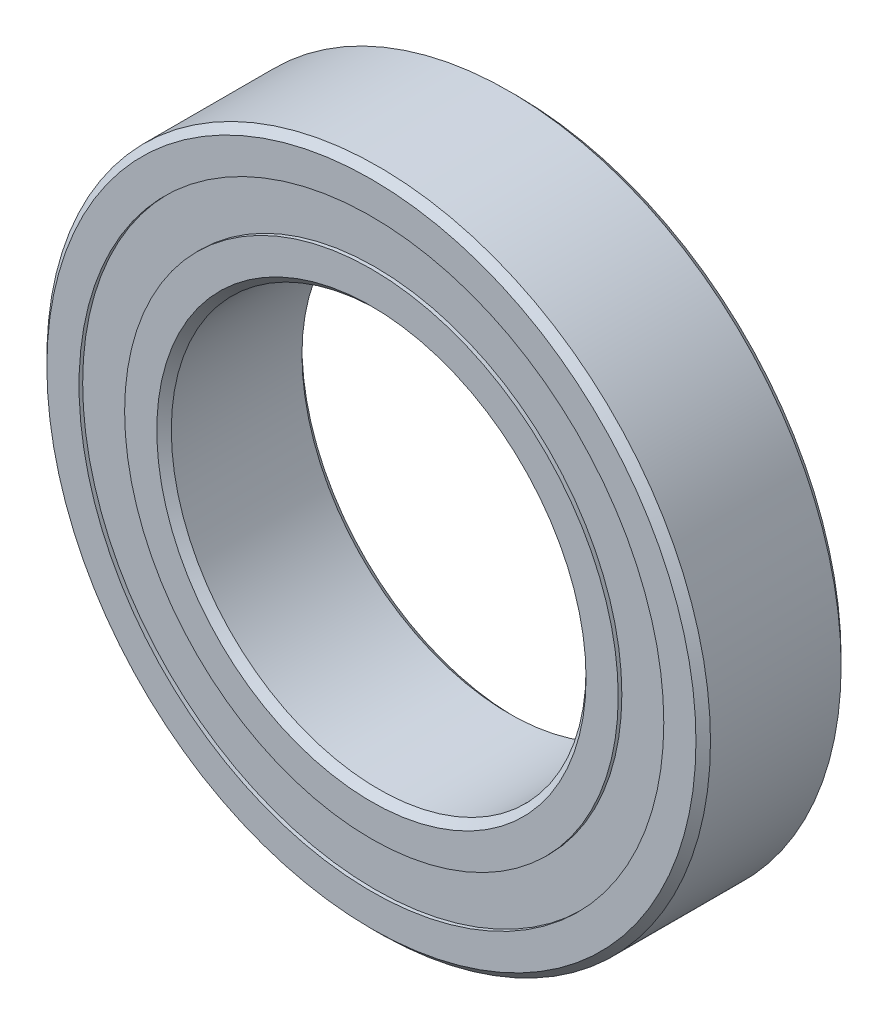
SolidWorks part; units mm, degrees
ref_plane "Front Plane" through (0, 0, 0) normal (0, 0, 1) x (1, 0, 0)
ref_plane "Top Plane" through (0, 0, 0) normal (0, 1, 0) x (1, 0, 0)
ref_plane "Right Plane" through (0, 0, 0) normal (1, 0, 0) x (0, 0, -1)
sketch "Sketch1" plane through (0, 0, 0) normal (0, 0, 1) x (1, 0, 0)
  circle A0 centre (0, 0) radius 16 construction
  circle A1 centre (0, 0) radius 10 construction
  dimension "OD" = 32
  dimension "Shaft Dia" = 20
sketch "Sketch2" plane through (0, 0, 0) normal (1, 0, 0) x (0, 0, -1)
  line L0 (-3.5, 0) -> (3.5, 0) construction
  line L1 (0, 16) -> (0, -16) construction
  line L2 (3.15, 16) -> (-3.15, 16) construction
  line L3 (-3.15, 16) -> (-3.5, 15.65) construction
  line L4 (-3.5, 15.65) -> (-3.5, 14.0989) construction
  line L5 (-3.5, 14.0989) -> (-1.5556, 14.0989) construction
  line L6 (3.5, 14.0989) -> (1.5556, 14.0989) construction
  line L7 (3.5, 15.65) -> (3.5, 14.0989) construction
  line L8 (3.15, 16) -> (3.5, 15.65) construction
  line L9 (0, 16) -> (0, 13) construction
  line L10 (0, 13) -> (0, 10) construction
  line L11 (3.5, 13) -> (-3.5, 13) construction
  line L12 (-3.5, 10.35) -> (-3.5, 11.9011) construction
  line L13 (-3.15, 10) -> (-3.5, 10.35) construction
  line L14 (3.15, 10) -> (-3.15, 10) construction
  line L15 (3.15, 10) -> (3.5, 10.35) construction
  line L16 (3.5, 10.35) -> (3.5, 11.9011) construction
  line L17 (3.5, 11.9011) -> (1.5556, 11.9011) construction
  line L18 (-3.5, 11.9011) -> (-1.5556, 11.9011) construction
  arc A0 (-1.5556, 14.0989) -> (1.5556, 14.0989) centre (0, 13) cw construction
  arc A1 (-1.5556, 11.9011) -> (1.5556, 11.9011) centre (0, 13) ccw construction
  point P14 (0, 10)
  point P18 (0, 13)
  dimension "D1" = 45
  dimension "D2" = 0.35
  dimension "D3" = 3.1111
  dimension "D4" = 1.0989
  dimension "Width" = 7
sketch "Sketch6" plane through (0, 0, 0) normal (1, 0, 0) x (0, 0, -1)
  line L0 (-3.5, 15.65) -> (-3.5, 14.0989) construction
  line L1 (-3.15, 16) -> (-3.5, 15.65) construction
  line L2 (3.15, 16) -> (-3.15, 16) construction
  line L3 (3.15, 16) -> (3.5, 15.65) construction
  line L4 (3.5, 15.65) -> (3.5, 14.0989) construction
  line L5 (3.5, 14.0989) -> (1.5556, 14.0989) construction
  line L6 (-3.5, 14.0989) -> (-1.5556, 14.0989) construction
  line L7 (-3.5, 15.65) -> (-3.5, 14.0989)
  line L8 (-3.15, 16) -> (-3.5, 15.65)
  line L9 (3.15, 16) -> (-3.15, 16)
  line L10 (3.15, 16) -> (3.5, 15.65)
  line L11 (3.5, 15.65) -> (3.5, 14.0989)
  line L12 (3.5, 14.0989) -> (1.5556, 14.0989)
  line L13 (-3.5, 14.0989) -> (-1.5556, 14.0989)
  line L14 (-3.5, 10.35) -> (-3.5, 11.9011) construction
  line L15 (-3.15, 10) -> (-3.5, 10.35) construction
  line L16 (3.15, 10) -> (-3.15, 10) construction
  line L17 (3.15, 10) -> (3.5, 10.35) construction
  line L18 (3.5, 10.35) -> (3.5, 11.9011) construction
  line L19 (3.5, 11.9011) -> (1.5556, 11.9011) construction
  line L20 (-3.5, 11.9011) -> (-1.5556, 11.9011) construction
  line L21 (-3.5, 10.35) -> (-3.5, 11.9011)
  line L22 (-3.15, 10) -> (-3.5, 10.35)
  line L23 (3.15, 10) -> (-3.15, 10)
  line L24 (3.15, 10) -> (3.5, 10.35)
  line L25 (3.5, 10.35) -> (3.5, 11.9011)
  line L26 (3.5, 11.9011) -> (1.5556, 11.9011)
  line L27 (-3.5, 11.9011) -> (-1.5556, 11.9011)
  arc A0 (1.5556, 14.0989) -> (-1.5556, 14.0989) centre (0, 13) ccw construction
  arc A1 (1.5556, 14.0989) -> (-1.5556, 14.0989) centre (0, 13) ccw
  arc A2 (-1.5556, 11.9011) -> (1.5556, 11.9011) centre (0, 13) ccw construction
  arc A3 (-1.5556, 11.9011) -> (1.5556, 11.9011) centre (0, 13) ccw
revolve "Revolve1" add sketch "Sketch6" angle 360 about L0
sketch "Sketch4" plane through (0, 0, 0) normal (1, 0, 0) x (0, 0, -1)
  line L0 (-1.9046, 13) -> (1.9046, 13)
  arc A2 (-1.9046, 13) -> (1.9046, 13) centre (0, 13) cw
  arc A3 (1.5556, 14.0989) -> (-1.5556, 14.0989) centre (0, 13) ccw construction
revolve "Revolve2" add sketch "Sketch4" angle 360 about L0
ref_axis "Axis1" through (0, 0, -3.5) along (0, 0, 1)
pattern_circular "CirPattern1" count 12 every 30 about axis through (0, 0, -3.5) along (0, 0, 1) of bodies 104
sketch "Sketch5" plane through (0, 0, 0) normal (1, 0, 0) x (0, 0, -1)
  line L0 (-3.5, 14.0989) -> (-1.5556, 14.0989) construction
  line L1 (-3.325, 14.0989) -> (-1.9046, 14.0989)
  line L2 (-3.325, 14.0989) -> (-3.325, 11.9011)
  line L3 (-3.325, 11.9011) -> (-1.9046, 11.9011)
  line L4 (-1.9046, 14.0989) -> (-1.9046, 11.9011)
  line L6 (3.5, 14.0989) -> (1.5556, 14.0989) construction
  line L7 (3.325, 14.0989) -> (1.9046, 14.0989)
  line L8 (3.325, 14.0989) -> (3.325, 11.9011)
  line L9 (3.325, 11.9011) -> (1.9046, 11.9011)
  line L10 (1.9046, 14.0989) -> (1.9046, 11.9011)
  line L12 (-3.15, 16) -> (-3.5, 15.65) construction
  line L13 (-3.5, 11.9011) -> (-1.5556, 11.9011) construction
  line L14 (3.5, 11.9011) -> (1.5556, 11.9011) construction
  point P18 (-3.325, 15.825)
revolve "Revolve3" add sketch "Sketch5" angle 360 about L0
equation "\"D2@Sketch2\"= \"Width@Sketch2\" * .05"
equation "\"D3@Sketch2\"=\"Width@Sketch2\" / 2.25"
equation "\"D4@Sketch2\"= ( ( ( \"OD@Sketch1\" - \"Width@Sketch2\" ) / 2 ) / 3.25 ) / 3.5"
equation "\"D2@CirPattern1\" = 360/\"Balls@CirPattern1\""
